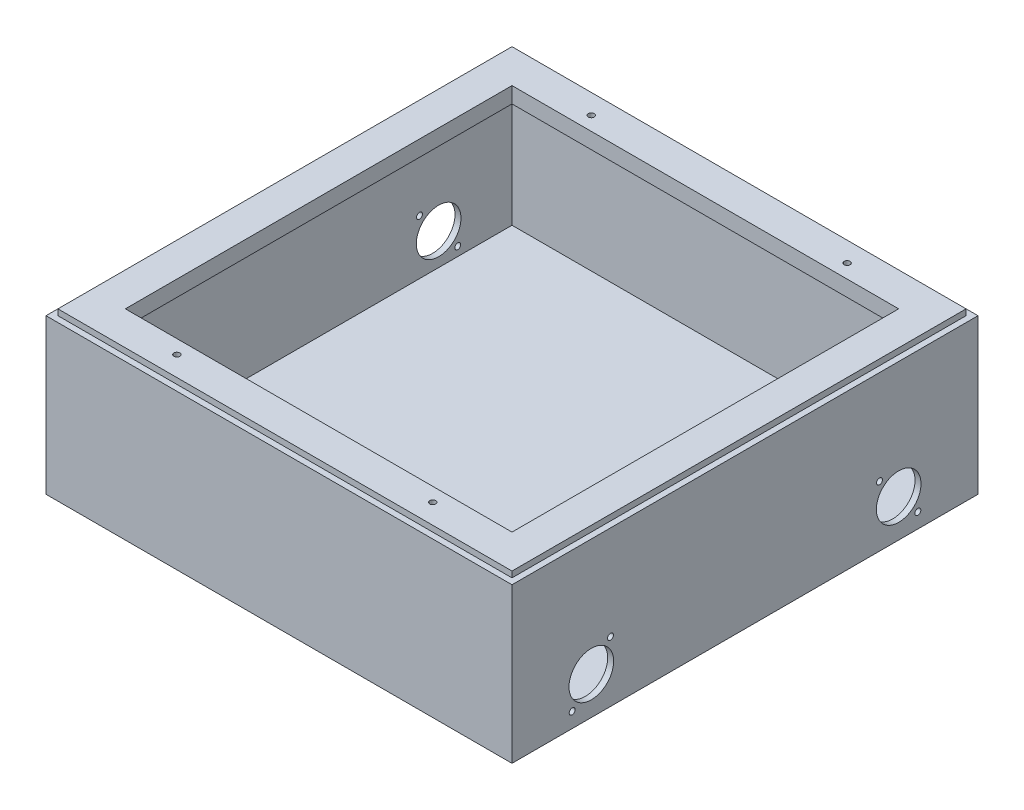
SolidWorks part; units mm, degrees
material "3003 Alloy"
ref_plane "Front Plane" through (0, 0, 0) normal (0, 0, 1) x (1, 0, 0)
ref_plane "Top Plane" through (0, 0, 0) normal (0, 1, 0) x (1, 0, 0)
ref_plane "Right Plane" through (0, 0, 0) normal (1, 0, 0) x (0, 0, -1)
sketch "Sketch2" plane through (0, 0, 0) normal (0, 1, 0) x (1, 0, 0)
  line L1 (0, 0) -> (235, 0)
  line L2 (0, 0) -> (0, -235)
  line L3 (0, -235) -> (235, -235)
  line L4 (235, 0) -> (235, -235)
  dimension "D1" = 235
  dimension "D2" = 235
extrude "Boss-Extrude1" add sketch "Sketch2" along normal blind 3
sketch "Sketch3" plane through (0, 3, 0) normal (0, 1, 0) x (1, 0, 0)
  line L0 (235, -235) -> (235, 0) construction
  line L1 (0, 0) -> (3, 0)
  line L2 (0, 0) -> (0, -3)
  line L3 (3, -3) -> (232, -3)
  line L4 (235, 0) -> (235, -3)
  line L7 (3, -232) -> (232, -232)
  line L8 (235, -235) -> (235, -232)
  line L9 (0, -235) -> (235, -235)
  line L10 (0, -235) -> (0, -232)
  line L15 (232, 0) -> (235, 0)
  line L16 (0, 0) -> (3, 0)
  line L17 (0, 0) -> (0, -235)
  line L18 (0, -235) -> (3, -235)
  line L19 (3, -3) -> (3, -232)
  line L20 (235, -235) -> (232, -235)
  line L21 (232, -3) -> (232, -232)
  line L22 (235, 0) -> (232, 0)
  line L23 (235, 0) -> (235, -235)
  line M5 (0, 0) -> (0, -235)
  line M6 (0, -235) -> (235, -235)
  line M7 (235, -235) -> (235, 0)
  line M8 (235, 0) -> (0, 0)
  dimension "D1" = 3
  dimension "D2" = 3
  dimension "D3" = 229
  dimension "D4" = 229
  dimension "D5" = 90
  dimension "D6" = 90
extrude "Boss-Extrude3" add sketch "Sketch3" along normal blind 75 contours L9 L3 L21 L7 L19 M8 M5 M6 M7 region at (1.5, 3, 3.3234)
sketch "Sketch6" plane through (0, 78, 0) normal (0, 1, 0) x (1, 0, 0)
  line L0 (235, -235) -> (235, 0) construction
  line L1 (0, 0) -> (235, 0)
  line L2 (0, 0) -> (0, -20)
  line L3 (20, -20) -> (215, -20)
  line L4 (235, 0) -> (235, -20)
  line L5 (0, -235) -> (235, -235) construction
  line L6 (235, 0) -> (215, 0)
  line L7 (235, 0) -> (235, -235)
  line L8 (235, -235) -> (215, -235)
  line L9 (215, -20) -> (215, -215)
  line L11 (0, 0) -> (20, 0)
  line L12 (0, 0) -> (0, -235)
  line L13 (0, -235) -> (20, -235)
  line L14 (20, -20) -> (20, -215)
  line L15 (0, -235) -> (235, -235)
  line L16 (0, -235) -> (0, -215)
  line L17 (20, -215) -> (215, -215)
  line L18 (235, -235) -> (235, -215)
  line L20 (3, -3) -> (3, -232) construction
  line L21 (3, -3) -> (232, -3) construction
  line L22 (117.5, -3) -> (117.5, -232) construction
  line L23 (3, -3) -> (232, -3) construction
  line L24 (3, -232) -> (232, -232) construction
  line L25 (0, -117.5) -> (235, -117.5) construction
  circle A0 centre (53, -13) radius 1.5
  circle A1 centre (182, -13) radius 1.5
  circle A2 centre (182, -222) radius 1.5
  circle A3 centre (53, -222) radius 1.5
  line M13 (3, -3) -> (232, -3)
  line M14 (232, -3) -> (232, -232)
  line M15 (232, -232) -> (3, -232)
  line M16 (3, -232) -> (3, -3)
  dimension "D6" = 3
  dimension "D7" = 50
  dimension "D1" = 20
  dimension "D2" = 20
  dimension "D3" = 20
  dimension "D4" = 20
  dimension "D5" = 20
  dimension "D8" = 10
extrude "Boss-Extrude4" add sketch "Sketch6" along normal blind 3 separate body contours L17 L14 L3 L9 M13 M16 M15 M14 region at (117.5, 78, 6.2385)
sketch "Sketch9" plane through (235, 0, 0) normal (1, 0, 0) x (0, 0, -1)
  line L0 (-235, 0) -> (0, 0) construction
  line L2 (-235, 78) -> (-235, 0) construction
  line L3 (-117.5, 78) -> (-117.5, 0)
  line L4 (-3, 78) -> (-232, 78) construction
  line L7 (-195, 19) -> (-190.5708, 15.2724)
  circle A0 centre (-195, 19) radius 11.255
  circle A1 centre (-40, 19) radius 11.255
  circle A4 centre (-185.3414, 30.4765) radius 1.5
  circle A5 centre (-204.6586, 7.5235) radius 1.5
  circle A6 centre (-30.3414, 7.5235) radius 1.5
  circle A7 centre (-49.6586, 30.4765) radius 1.5
  dimension "D1" = 30
  dimension "D2" = 22.51
  dimension "D3" = 15
  dimension "D6" = 3
  dimension "D4" = 19
  dimension "D7" = 7.5235
  dimension "D5" = 40
extrude "Cut-Extrude1" cut sketch "Sketch9" against normal blind 600 and the other way blind 600 contours A0 | A1 | A4 | A5 | A7 | A6 region at (235, 19, 205.9367) region at (235, 19, 40)
sketch "Sketch12" plane through (0, 78, 0) normal (0, -1, 0) x (1, 0, 0)
  line L0 (0, 235) -> (235, 235)
  line L1 (235, 235) -> (235, 0)
  line L2 (235, 0) -> (0, 0)
  line L3 (0, 0) -> (0, 235)
  line L4 (20, 215) -> (215, 215)
  line L5 (215, 215) -> (215, 20)
  line L6 (215, 20) -> (20, 20)
  line L7 (20, 20) -> (20, 215)
  line L8 (232, 3) -> (232, 232) construction
  dimension "D1" = 20
  dimension "D2" = 20
  dimension "D3" = 20
  dimension "D4" = 17
extrude "Boss-Extrude5" add sketch "Sketch12" along normal blind 5
